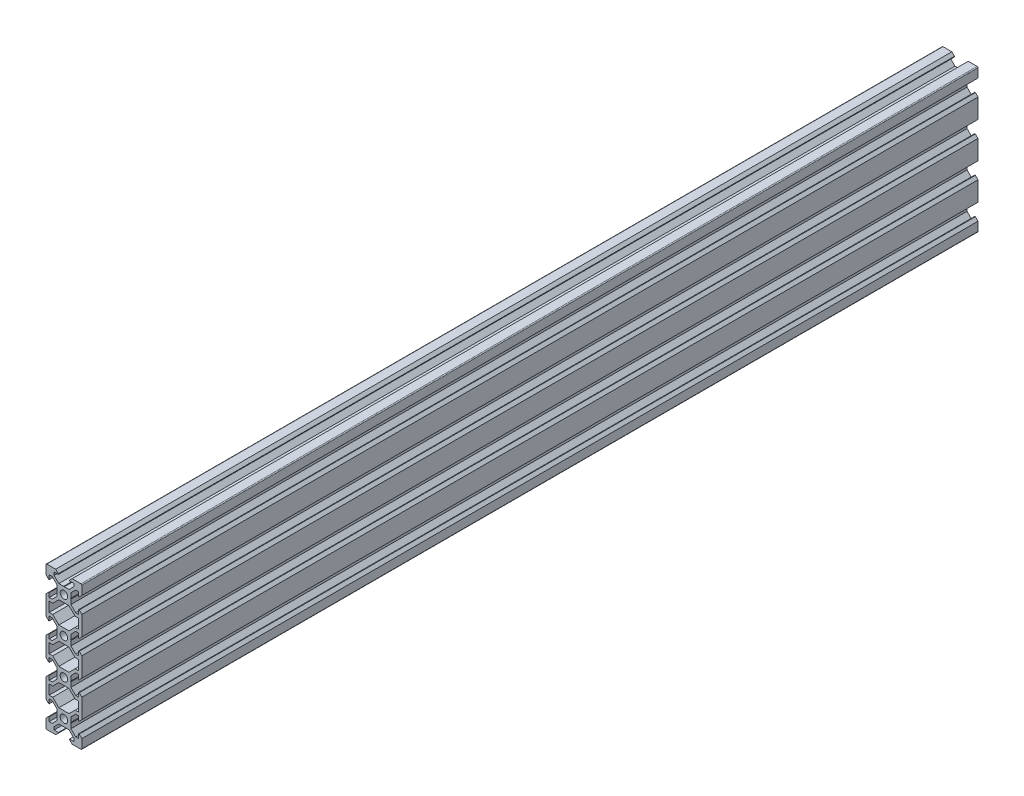
SolidWorks part; units mm, degrees
material "6061-T6 (SS)"
ref_plane "Front Plane" through (0, 0, 0) normal (0, 0, 1) x (1, 0, 0)
ref_plane "Top Plane" through (0, 0, 0) normal (0, 1, 0) x (1, 0, 0)
ref_plane "Right Plane" through (0, 0, 0) normal (1, 0, 0) x (0, 0, -1)
sketch "Sketch1" plane through (0, 0, 0) normal (0, 0, 1) x (1, 0, 0)
  line L0 (0, 0) -> (10, 0) construction
  line L1 (9.5, -40) -> (-9.5, -40)
  line L2 (10, -39.5) -> (10, 39.5)
  line L3 (9.5, 40) -> (-9.5, 40)
  line L4 (-10, -39.5) -> (-10, 39.5)
  line L5 (10, -40) -> (-10, 40) construction
  line L6 (10, 40) -> (-10, -40) construction
  circle A0 centre (0, 30) radius 2.1
  circle A1 centre (0, 10) radius 2.1
  circle A2 centre (0, -10) radius 2.1
  circle A3 centre (0, -30) radius 2.1
  arc A4 (-9.5, -40) -> (-10, -39.5) centre (-9.5, -39.5) cw
  arc A5 (9.5, -40) -> (10, -39.5) centre (9.5, -39.5) ccw
  arc A6 (10, 39.5) -> (9.5, 40) centre (9.5, 39.5) ccw
  arc A7 (-9.5, 40) -> (-10, 39.5) centre (-9.5, 39.5) ccw
  point P0 (0, 0)
  line B0 (0, 30) -> (0, 40) construction
  line B1 (0, 33.69) -> (-0.21, 33.9)
  line B2 (-0.21, 33.9) -> (-2.8393, 33.9)
  line B3 (-2.8393, 33.9) -> (-5.5, 36.5607)
  line B4 (-5.5, 36.5607) -> (-5.5, 38.2)
  line B5 (-5.5, 38.2) -> (-3.125, 38.2)
  line B6 (-3.125, 38.2) -> (-3.125, 38.545)
  line B7 (-3.125, 38.545) -> (-4.58, 40)
  line B8 (-4.58, 40) -> (4.58, 40)
  line B9 (0, 30) -> (-5.9132, 35.9132) construction
  line B10 (3.125, 38.545) -> (4.58, 40)
  line B11 (3.125, 38.2) -> (3.125, 38.545)
  line B12 (5.5, 38.2) -> (3.125, 38.2)
  line B13 (5.5, 36.5607) -> (5.5, 38.2)
  line B14 (2.8393, 33.9) -> (5.5, 36.5607)
  line B15 (0.21, 33.9) -> (2.8393, 33.9)
  line B16 (0, 33.69) -> (0.21, 33.9)
  line B17 (0, 30) -> (-10, 30) construction
  line B18 (-3.69, 30) -> (-3.9, 29.79)
  line B19 (-3.9, 29.79) -> (-3.9, 27.1607)
  line B20 (-3.9, 27.1607) -> (-6.5607, 24.5)
  line B21 (-6.5607, 24.5) -> (-8.2, 24.5)
  line B22 (-8.2, 24.5) -> (-8.2, 26.875)
  line B23 (-8.2, 26.875) -> (-8.545, 26.875)
  line B24 (-8.545, 26.875) -> (-10, 25.42)
  line B25 (-10, 25.42) -> (-10, 34.58)
  line B26 (0, 30) -> (-5.9132, 24.0868) construction
  line B27 (-8.545, 33.125) -> (-10, 34.58)
  line B28 (-8.2, 33.125) -> (-8.545, 33.125)
  line B29 (-8.2, 35.5) -> (-8.2, 33.125)
  line B30 (-6.5607, 35.5) -> (-8.2, 35.5)
  line B31 (-3.9, 32.8393) -> (-6.5607, 35.5)
  line B32 (-3.9, 30.21) -> (-3.9, 32.8393)
  line B33 (-3.69, 30) -> (-3.9, 30.21)
  line B34 (0, 10) -> (-10, 10) construction
  line B35 (-3.69, 10) -> (-3.9, 9.79)
  line B36 (-3.9, 9.79) -> (-3.9, 7.1607)
  line B37 (-3.9, 7.1607) -> (-6.5607, 4.5)
  line B38 (-6.5607, 4.5) -> (-8.2, 4.5)
  line B39 (-8.2, 4.5) -> (-8.2, 6.875)
  line B40 (-8.2, 6.875) -> (-8.545, 6.875)
  line B41 (-8.545, 6.875) -> (-10, 5.42)
  line B42 (-10, 5.42) -> (-10, 14.58)
  line B43 (0, 10) -> (-5.9132, 4.0868) construction
  line B44 (-8.545, 13.125) -> (-10, 14.58)
  line B45 (-8.2, 13.125) -> (-8.545, 13.125)
  line B46 (-8.2, 15.5) -> (-8.2, 13.125)
  line B47 (-6.5607, 15.5) -> (-8.2, 15.5)
  line B48 (-3.9, 12.8393) -> (-6.5607, 15.5)
  line B49 (-3.9, 10.21) -> (-3.9, 12.8393)
  line B50 (-3.69, 10) -> (-3.9, 10.21)
  line B51 (0, -10) -> (-10, -10) construction
  line B52 (-3.69, -10) -> (-3.9, -10.21)
  line B53 (-3.9, -10.21) -> (-3.9, -12.8393)
  line B54 (-3.9, -12.8393) -> (-6.5607, -15.5)
  line B55 (-6.5607, -15.5) -> (-8.2, -15.5)
  line B56 (-8.2, -15.5) -> (-8.2, -13.125)
  line B57 (-8.2, -13.125) -> (-8.545, -13.125)
  line B58 (-8.545, -13.125) -> (-10, -14.58)
  line B59 (-10, -14.58) -> (-10, -5.42)
  line B60 (0, -10) -> (-5.9132, -15.9132) construction
  line B61 (-8.545, -6.875) -> (-10, -5.42)
  line B62 (-8.2, -6.875) -> (-8.545, -6.875)
  line B63 (-8.2, -4.5) -> (-8.2, -6.875)
  line B64 (-6.5607, -4.5) -> (-8.2, -4.5)
  line B65 (-3.9, -7.1607) -> (-6.5607, -4.5)
  line B66 (-3.9, -9.79) -> (-3.9, -7.1607)
  line B67 (-3.69, -10) -> (-3.9, -9.79)
  line B68 (0, -30) -> (-10, -30) construction
  line B69 (-3.69, -30) -> (-3.9, -30.21)
  line B70 (-3.9, -30.21) -> (-3.9, -32.8393)
  line B71 (-3.9, -32.8393) -> (-6.5607, -35.5)
  line B72 (-6.5607, -35.5) -> (-8.2, -35.5)
  line B73 (-8.2, -35.5) -> (-8.2, -33.125)
  line B74 (-8.2, -33.125) -> (-8.545, -33.125)
  line B75 (-8.545, -33.125) -> (-10, -34.58)
  line B76 (-10, -34.58) -> (-10, -25.42)
  line B77 (0, -30) -> (-5.9132, -35.9132) construction
  line B78 (-8.545, -26.875) -> (-10, -25.42)
  line B79 (-8.2, -26.875) -> (-8.545, -26.875)
  line B80 (-8.2, -24.5) -> (-8.2, -26.875)
  line B81 (-6.5607, -24.5) -> (-8.2, -24.5)
  line B82 (-3.9, -27.1607) -> (-6.5607, -24.5)
  line B83 (-3.9, -29.79) -> (-3.9, -27.1607)
  line B84 (-3.69, -30) -> (-3.9, -29.79)
  line B85 (0, -30) -> (0, -40) construction
  line B86 (0, -33.69) -> (0.21, -33.9)
  line B87 (0.21, -33.9) -> (2.8393, -33.9)
  line B88 (2.8393, -33.9) -> (5.5, -36.5607)
  line B89 (5.5, -36.5607) -> (5.5, -38.2)
  line B90 (5.5, -38.2) -> (3.125, -38.2)
  line B91 (3.125, -38.2) -> (3.125, -38.545)
  line B92 (3.125, -38.545) -> (4.58, -40)
  line B93 (4.58, -40) -> (-4.58, -40)
  line B94 (0, -30) -> (5.9132, -35.9132) construction
  line B95 (-3.125, -38.545) -> (-4.58, -40)
  line B96 (-3.125, -38.2) -> (-3.125, -38.545)
  line B97 (-5.5, -38.2) -> (-3.125, -38.2)
  line B98 (-5.5, -36.5607) -> (-5.5, -38.2)
  line B99 (-2.8393, -33.9) -> (-5.5, -36.5607)
  line B100 (-0.21, -33.9) -> (-2.8393, -33.9)
  line B101 (0, -33.69) -> (-0.21, -33.9)
  line B102 (0, -30) -> (10, -30) construction
  line B103 (3.69, -30) -> (3.9, -29.79)
  line B104 (3.9, -29.79) -> (3.9, -27.1607)
  line B105 (3.9, -27.1607) -> (6.5607, -24.5)
  line B106 (6.5607, -24.5) -> (8.2, -24.5)
  line B107 (8.2, -24.5) -> (8.2, -26.875)
  line B108 (8.2, -26.875) -> (8.545, -26.875)
  line B109 (8.545, -26.875) -> (10, -25.42)
  line B110 (10, -25.42) -> (10, -34.58)
  line B111 (0, -30) -> (5.9132, -24.0868) construction
  line B112 (8.545, -33.125) -> (10, -34.58)
  line B113 (8.2, -33.125) -> (8.545, -33.125)
  line B114 (8.2, -35.5) -> (8.2, -33.125)
  line B115 (6.5607, -35.5) -> (8.2, -35.5)
  line B116 (3.9, -32.8393) -> (6.5607, -35.5)
  line B117 (3.9, -30.21) -> (3.9, -32.8393)
  line B118 (3.69, -30) -> (3.9, -30.21)
  line B119 (0, -10) -> (10, -10) construction
  line B120 (3.69, -10) -> (3.9, -9.79)
  line B121 (3.9, -9.79) -> (3.9, -7.1607)
  line B122 (3.9, -7.1607) -> (6.5607, -4.5)
  line B123 (6.5607, -4.5) -> (8.2, -4.5)
  line B124 (8.2, -4.5) -> (8.2, -6.875)
  line B125 (8.2, -6.875) -> (8.545, -6.875)
  line B126 (8.545, -6.875) -> (10, -5.42)
  line B127 (10, -5.42) -> (10, -14.58)
  line B128 (0, -10) -> (5.9132, -4.0868) construction
  line B129 (8.545, -13.125) -> (10, -14.58)
  line B130 (8.2, -13.125) -> (8.545, -13.125)
  line B131 (8.2, -15.5) -> (8.2, -13.125)
  line B132 (6.5607, -15.5) -> (8.2, -15.5)
  line B133 (3.9, -12.8393) -> (6.5607, -15.5)
  line B134 (3.9, -10.21) -> (3.9, -12.8393)
  line B135 (3.69, -10) -> (3.9, -10.21)
  line B136 (0, 10) -> (10, 10) construction
  line B137 (3.69, 10) -> (3.9, 10.21)
  line B138 (3.9, 10.21) -> (3.9, 12.8393)
  line B139 (3.9, 12.8393) -> (6.5607, 15.5)
  line B140 (6.5607, 15.5) -> (8.2, 15.5)
  line B141 (8.2, 15.5) -> (8.2, 13.125)
  line B142 (8.2, 13.125) -> (8.545, 13.125)
  line B143 (8.545, 13.125) -> (10, 14.58)
  line B144 (10, 14.58) -> (10, 5.42)
  line B145 (0, 10) -> (5.9132, 15.9132) construction
  line B146 (8.545, 6.875) -> (10, 5.42)
  line B147 (8.2, 6.875) -> (8.545, 6.875)
  line B148 (8.2, 4.5) -> (8.2, 6.875)
  line B149 (6.5607, 4.5) -> (8.2, 4.5)
  line B150 (3.9, 7.1607) -> (6.5607, 4.5)
  line B151 (3.9, 9.79) -> (3.9, 7.1607)
  line B152 (3.69, 10) -> (3.9, 9.79)
  line B153 (0, 30) -> (10, 30) construction
  line B154 (3.69, 30) -> (3.9, 30.21)
  line B155 (3.9, 30.21) -> (3.9, 32.8393)
  line B156 (3.9, 32.8393) -> (6.5607, 35.5)
  line B157 (6.5607, 35.5) -> (8.2, 35.5)
  line B158 (8.2, 35.5) -> (8.2, 33.125)
  line B159 (8.2, 33.125) -> (8.545, 33.125)
  line B160 (8.545, 33.125) -> (10, 34.58)
  line B161 (10, 34.58) -> (10, 25.42)
  line B162 (0, 30) -> (5.9132, 35.9132) construction
  line B163 (8.545, 26.875) -> (10, 25.42)
  line B164 (8.2, 26.875) -> (8.545, 26.875)
  line B165 (8.2, 24.5) -> (8.2, 26.875)
  line B166 (6.5607, 24.5) -> (8.2, 24.5)
  line B167 (3.9, 27.1607) -> (6.5607, 24.5)
  line B168 (3.9, 29.79) -> (3.9, 27.1607)
  line B169 (3.69, 30) -> (3.9, 29.79)
  line B170 (-8.2, 17.3) -> (-8.2, 22.7)
  line B171 (-8.2, 22.7) -> (-6.2393, 22.7)
  line B172 (-6.2393, 22.7) -> (-2.8393, 26.1)
  line B173 (-2.8393, 26.1) -> (2.8393, 26.1)
  line B174 (0, 26.1) -> (0, 20) construction
  line B175 (0, 20) -> (-8.2, 20) construction
  line B176 (6.2393, 22.7) -> (2.8393, 26.1)
  line B177 (8.2, 22.7) -> (6.2393, 22.7)
  line B178 (8.2, 17.3) -> (8.2, 22.7)
  line B179 (8.2, 17.3) -> (6.2393, 17.3)
  line B180 (6.2393, 17.3) -> (2.8393, 13.9)
  line B181 (-2.8393, 13.9) -> (2.8393, 13.9)
  line B182 (-6.2393, 17.3) -> (-2.8393, 13.9)
  line B183 (-8.2, 17.3) -> (-6.2393, 17.3)
  line B184 (0, 26.1) -> (0, 30) construction
  line B185 (0, 30) -> (-5.0927, 24.9073) construction
  line B186 (-8.2, -2.7) -> (-8.2, 2.7)
  line B187 (-8.2, 2.7) -> (-6.2393, 2.7)
  line B188 (-6.2393, 2.7) -> (-2.8393, 6.1)
  line B189 (-2.8393, 6.1) -> (2.8393, 6.1)
  line B190 (0, 6.1) -> (0, 0) construction
  line B191 (0, 0) -> (-8.2, 0) construction
  line B192 (6.2393, 2.7) -> (2.8393, 6.1)
  line B193 (8.2, 2.7) -> (6.2393, 2.7)
  line B194 (8.2, -2.7) -> (8.2, 2.7)
  line B195 (8.2, -2.7) -> (6.2393, -2.7)
  line B196 (6.2393, -2.7) -> (2.8393, -6.1)
  line B197 (-2.8393, -6.1) -> (2.8393, -6.1)
  line B198 (-6.2393, -2.7) -> (-2.8393, -6.1)
  line B199 (-8.2, -2.7) -> (-6.2393, -2.7)
  line B200 (0, 6.1) -> (0, 10) construction
  line B201 (0, 10) -> (-5.0927, 4.9073) construction
  line B202 (-8.2, -22.7) -> (-8.2, -17.3)
  line B203 (-8.2, -17.3) -> (-6.2393, -17.3)
  line B204 (-6.2393, -17.3) -> (-2.8393, -13.9)
  line B205 (-2.8393, -13.9) -> (2.8393, -13.9)
  line B206 (0, -13.9) -> (0, -20) construction
  line B207 (0, -20) -> (-8.2, -20) construction
  line B208 (6.2393, -17.3) -> (2.8393, -13.9)
  line B209 (8.2, -17.3) -> (6.2393, -17.3)
  line B210 (8.2, -22.7) -> (8.2, -17.3)
  line B211 (8.2, -22.7) -> (6.2393, -22.7)
  line B212 (6.2393, -22.7) -> (2.8393, -26.1)
  line B213 (-2.8393, -26.1) -> (2.8393, -26.1)
  line B214 (-6.2393, -22.7) -> (-2.8393, -26.1)
  line B215 (-8.2, -22.7) -> (-6.2393, -22.7)
  line B216 (0, -13.9) -> (0, -10) construction
  line B217 (0, -10) -> (-5.0927, -15.0927) construction
  dimension "D5" = 4.2
  dimension "D1" = 20
  dimension "D2" = 80
  dimension "D3" = 20
  dimension "D4" = 20
sketch_block_instance "V Slot 1-4"
sketch_block "V Slot 1" parameters "D1"=10, "D2"=11, "D3"=4.3, "D4"=1.8, "D5"=0.21, "D6"=45, "D7"=9.16, "D8"=1.5, "D9"=6.25
sketch_block_instance "V Slot 1-5"
sketch_block_instance "V Slot 1-6"
sketch_block_instance "V Slot 1-7"
sketch_block_instance "V Slot 1-8"
sketch_block_instance "V Slot 1-9"
sketch_block_instance "V Slot 1-10"
sketch_block_instance "V Slot 1-11"
sketch_block_instance "V Slot 1-12"
sketch_block_instance "V Slot 1-13"
sketch_block_instance "Center Cutout 1-1"
sketch_block "Center Cutout 1" parameters "D1"=5.4, "D2"=12.2, "D3"=8.2, "D4"=45, "D5"=10, "D6"=1.5
sketch_block_instance "Center Cutout 1-2"
sketch_block_instance "Center Cutout 1-3" parameters "D5"=5.9516, "D6"=0.5, "D1"=53.3893, "D2"=54.3269, "D3"=11.952, "D4"=27.681
extrude "Boss-Extrude1" add sketch "Sketch1" along normal blind 500 contours B169 B154 B155 B156 B157 B158 B159 B160 L2 A6 L3 B10 B11 B12 B13 B14 B15 B16 B1 B2 B3 B4 B5 B6 B7 A7 L4 B27 B28 B29 B30 B31 B32 B33 B18 B19 B20 B21 B22 B23 B24 B44 B45 B46 B47 B48 B49 B50 B35 region at (7.04, -39.1754, 0)
